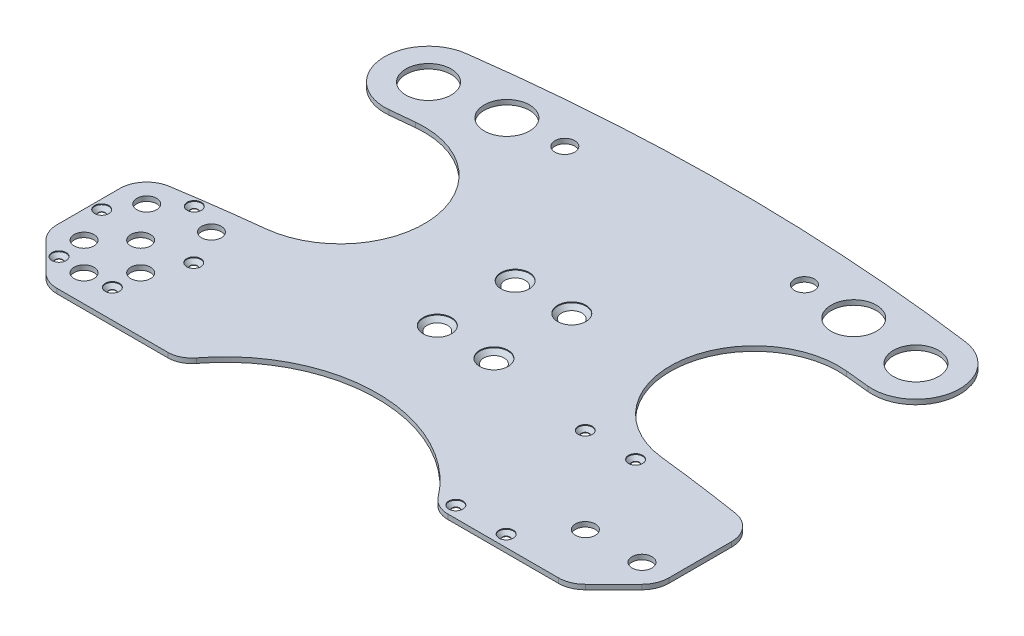
SolidWorks part; units mm, degrees
ref_plane "Front Plane" through (0, 0, 0) normal (0, 0, 1) x (1, 0, 0)
ref_plane "Top Plane" through (0, 0, 0) normal (0, 1, 0) x (1, 0, 0)
ref_plane "Right Plane" through (0, 0, 0) normal (1, 0, 0) x (0, 0, -1)
sketch "Sketch1" plane through (0, 0, 0) normal (0, 1, 0) x (1, 0, 0)
  line L1 (-120, -95) -> (120, -95)
  line L2 (-120, -95) -> (-120, 95)
  line L3 (-120, 95) -> (120, 95)
  line L4 (120, -95) -> (120, 95)
  line L5 (-120, -95) -> (120, 95) construction
  line L6 (-120, 95) -> (120, -95) construction
  line L7 (-10, 13.75) -> (10, 13.75)
  line L8 (-10, 13.75) -> (-10, -13.75)
  line L9 (-10, -13.75) -> (10, -13.75)
  line L10 (10, 13.75) -> (10, -13.75)
  line L11 (-10, 13.75) -> (10, -13.75) construction
  line L12 (-10, -13.75) -> (10, 13.75) construction
  circle A0 centre (0, 0) radius 95
  circle A1 centre (-10, 13.75) radius 2.5
  circle A2 centre (10, 13.75) radius 2.5
  circle A3 centre (10, -13.75) radius 2.5
  circle A4 centre (-10, -13.75) radius 2.5
  circle A5 centre (0, 0) radius 120
  dimension "D3" = 5
  dimension "D1" = 240
  dimension "D2" = 190
  dimension "D4" = 27.5
  dimension "D5" = 20
extrude "Boss-Extrude1" add sketch "Sketch1" along normal blind 1.7 contours A0 A4 L8 A1 L7 A2 L10 A3 L9 | A4 L9 A3 L10 A2 L7 A1 L8 | L3 A5 L1 A0 | L1 A5 L3 A0 region at (-105.6812, 0, 51.9346) region at (68.7642, 0, 68.7642) region at (-92.313, 0, 0) region at (0, 0, 0)
sketch "Sketch2" plane through (0, 1.7, 0) normal (0, 1, 0) x (1, 0, 0)
  line L0 (-81.1673, -40) -> (21.9115, -40) construction
  line L1 (-127.3056, -60) -> (138.909, -60) construction
  line L2 (-88.5406, 28.139) -> (-88.5406, -89.0376) construction
  line L3 (-88.5406, -40) -> (-88.5406, -60) construction
  line L4 (0, 21.6044) -> (0, -21.4213) construction
  line L5 (88.5406, 33.139) -> (88.5406, -84.0376) construction
  line L6 (-151.9803, -25) -> (55.006, -25) construction
  line L7 (-48.8837, 35) -> (62.426, 35) construction
  circle A0 centre (0, 0) radius 35
  circle A1 centre (0, 35) radius 2.5
  circle A2 centre (30.3109, 17.5) radius 2.5
  circle A3 centre (30.3109, -17.5) radius 2.5
  circle A4 centre (0, -35) radius 2.5
  circle A5 centre (-30.3109, -17.5) radius 2.5
  circle A6 centre (-30.3109, 17.5) radius 2.5
  circle A7 centre (-88.5406, -40) radius 3.5
  circle A8 centre (-88.5406, -50) radius 10
  circle A9 centre (-78.5406, -50) radius 3.5
  circle A10 centre (-88.5406, -60) radius 3.5
  circle A11 centre (-98.5406, -50) radius 3.5
  circle A12 centre (78.5406, -50) radius 3.5
  circle A13 centre (98.5406, -50) radius 3.5
  circle A14 centre (-98.5406, -27.8625) radius 3.5
  circle A15 centre (-78.5406, -25) radius 3.5
  circle A16 centre (0, 0) radius 45
  circle A17 centre (0, -580) radius 625
  circle A18 centre (0, -580) radius 645
  circle A19 centre (-86.0945, 59.2282) radius 8
  circle A20 centre (-61.2596, 62.0843) radius 8
  circle A21 centre (-86.0945, 59.2282) radius 15.5
  arc A22 (-73.3144, 95) -> (-73.3144, -95) centre (0, 0) ccw construction
  circle A23 centre (-61.2596, 62.0843) radius 9.5
  circle A24 centre (-86.0945, 59.2282) radius 9.5
  circle A25 centre (61.2596, 62.0843) radius 8
  circle A26 centre (86.0945, 59.2282) radius 8
  circle A27 centre (-42.3209, 63.6101) radius 3.5
  circle A28 centre (0, 0) radius 70
  circle A29 centre (42.3209, 63.6101) radius 3.5
  circle A30 centre (-98.5406, -50) radius 9.5
  circle A31 centre (42.3209, 63.6101) radius 9.5
  circle A32 centre (61.2596, 62.0843) radius 9.5
  circle A33 centre (0, -645.0455) radius 625
  point P17 (0, 0)
  point P21 (-88.5406, -50)
  point P37 (-88.5406, -50)
  point P56 (0, 65)
  point P57 (0, 45)
  point P68 (-76.6704, 60.4269)
  point P69 (-70.7097, 61.1124)
  point P81 (0, 0)
  point P85 (-98.5406, -27.8625)
  dimension "D1" = 70
  dimension "D2" = 5
  dimension "D4" = 7
  dimension "D9" = 90
  dimension "D10" = 1250
  dimension "D11" = 20
  dimension "D12" = 16
  dimension "D14" = 6
  dimension "D13" = 19
  dimension "D17" = 140
  dimension "D18" = 6
  dimension "D5" = 20
  dimension "D6" = 40
  dimension "D8" = 15
  dimension "D15" = 6
  dimension "D3" = 6
  dimension "D7" = 4
extrude "Cut-Extrude1" cut sketch "Sketch2" against normal up to next contours A7 | A9 | A10 | A11 | A12 | A13 | A14 | A15 | A19 | A20 | A25 | A26 | A27 | A29
sketch "Sketch3" plane through (0, 1.7, 0) normal (0, 1, 0) x (1, 0, 0)
  line L1 (-84.5506, 43.8053) -> (-40.7771, 48.1872)
  line L2 (0, 100.6986) -> (0, -98.8678) construction
  line L3 (-10.3445, 0) -> (20.4144, 0) construction
  line L5 (84.5506, 43.8053) -> (40.7771, 48.1872)
  line L6 (-42.3209, 63.6101) -> (0, 0) construction
  line L7 (-36.306, 26.5871) -> (-55.2257, 55.0243)
  line L8 (-10.4964, 43.7587) -> (-29.4161, 72.1959)
  line L9 (10.4964, 43.7587) -> (29.4161, 72.1959)
  line L10 (36.306, 26.5871) -> (55.2257, 55.0243)
  line L11 (-108.0406, -50) -> (-108.0406, -27.8625)
  line L13 (-73.3144, -95) -> (73.3144, -95)
  line L14 (73.3144, 95) -> (-73.3144, 95)
  line L15 (-73.3144, -95) -> (73.3144, -95)
  line L16 (73.3144, 95) -> (-73.3144, 95)
  line L17 (-69.0406, -25) -> (-69.0406, -50)
  line L18 (-71.8231, -56.7175) -> (-81.8231, -66.7175)
  line L19 (-105.2581, -56.7175) -> (-95.2581, -66.7175)
  line L20 (-42.3209, 79.1101) -> (42.3209, 79.1101)
  line L21 (-78.5406, -15.5) -> (-42.2463, -15.5)
  line L22 (0, -45) -> (111.243, -45) construction
  line L23 (-88.5406, -69.5) -> (88.5406, -69.5)
  line L24 (69.0406, -15.5) -> (45.0406, -15.5)
  line L25 (78.5406, -15.5) -> (42.2463, -15.5)
  line L27 (108.0406, -50) -> (108.0406, -27.8625)
  line L28 (105.2581, -56.7175) -> (95.2581, -66.7175)
  line L29 (69.0406, -15.5) -> (69.0406, -69.5)
  line L30 (69.0406, -69.5) -> (45.0406, -69.5)
  line L31 (45.0406, -15.5) -> (45.0406, -69.5)
  line L32 (57.0406, -15.5) -> (57.0406, -69.5) construction
  line L33 (45.0406, -42.5) -> (69.0406, -42.5) construction
  circle A0 centre (-86.0945, 59.2282) radius 15.5
  arc A1 (-73.3144, 95) -> (-73.3144, -95) centre (0, 0) ccw construction
  circle A2 centre (-42.3209, 63.6101) radius 15.5
  circle A3 centre (86.0945, 59.2282) radius 15.5
  circle A4 centre (42.3209, 63.6101) radius 15.5
  circle A5 centre (0, 0) radius 45
  circle A6 centre (-98.5406, -27.8625) radius 9.5
  circle A7 centre (-98.5406, -27.8625) radius 3.5 construction
  arc A8 (-73.3144, 95) -> (-73.3144, -95) centre (0, 0) ccw
  arc A9 (73.3144, -95) -> (73.3144, 95) centre (0, 0) ccw
  arc A10 (-73.3144, 95) -> (-73.3144, -95) centre (0, 0) ccw
  arc A11 (73.3144, -95) -> (73.3144, 95) centre (0, 0) ccw
  circle A12 centre (-78.5406, -25) radius 9.5
  circle A13 centre (-88.5406, -60) radius 9.5
  circle A14 centre (-98.5406, -50) radius 9.5
  circle A15 centre (-78.5406, -50) radius 9.5
  circle A17 centre (98.5406, -50) radius 9.5
  circle A18 centre (78.5406, -50) radius 9.5
  arc A19 (73.3144, -95) -> (73.3144, 95) centre (0, 0) ccw construction
  arc A20 (-45.0406, -69.5) -> (45.0406, -69.5) centre (0, -98.6511) cw
  circle A21 centre (98.5406, -27.8625) radius 9.5
  circle A22 centre (98.5406, -50) radius 9.5
  circle A23 centre (88.5406, -60) radius 9.5
  circle A24 centre (-73.1485, 15.1063) radius 29.692
  circle A25 centre (73.1485, 15.1063) radius 29.692
  circle A26 centre (48.1506, -19.64) radius 1.3
  circle A27 centre (65.9306, -19.64) radius 1.3
  circle A28 centre (65.9306, -65.36) radius 1.3
  circle A29 centre (48.1506, -65.36) radius 1.3
  circle A30 centre (0, -580) radius 645
  circle A31 centre (0, -580) radius 660.5
  circle A32 centre (0, -645.0455) radius 634.5
  point P20 (0, -659.5242)
  arc M45 (-73.3144, 95) -> (-73.3144, -95) centre (0, 0) ccw
  line M46 (-73.3144, -95) -> (73.3144, -95)
  arc M47 (73.3144, -95) -> (73.3144, 95) centre (0, 0) ccw
  line M48 (73.3144, 95) -> (-73.3144, 95)
  dimension "D1" = 90
  dimension "D3" = 6
  dimension "D5" = 2.6
  dimension "D4" = 24
  dimension "D6" = 17.78
  dimension "D7" = 45.72
  dimension "D2" = 0
extrude "Cut-Extrude2" cut sketch "Sketch3" against normal up to next contours A24 L1 A0 A14 L11 A6 L21 M45 | A24 | L28 A23 L23 A13 L19 A14 A10 A17 M46 M47 | A20 L23 | L5 A25 L24 L25 A21 L27 A17 A11 A3 | A25 | A30 A0 M45 | A31 A11 M48 M45 | A0 A31 A10 | A31 A3 M47 | A30 A3 M47 | A6 A32 A14 L11 M45 | A11 A32 A21 L27 A17 | A26 | A27 | A28 | A29 region at (-105.8887, 1.7, -12.959) region at (-73.1485, 1.7, -15.1063) region at (-102.839, 1.7, -59.5932) region at (-94.2652, 1.7, -72.7135) region at (0, 1.7, -86.2332) region at (-111.2756, 1.7, 31.2797) region at (0, 1.7, 81.3426) region at (0, 1.7, 59.4787) region at (73.1485, 1.7, -15.1063) region at (105.8887, 1.7, -12.959) region at (111.2756, 1.7, 31.2797) region at (94.2652, 1.7, -72.7135) region at (102.839, 1.7, -59.5932)
fillet "Fillet1" radius 8.5 2 edges at (45.0406, 0.85, 69.5) (-45.0406, 0.85, 69.5)
sketch "Sketch8" plane through (0, 1.7, 0) normal (0, 1, 0) x (1, 0, 0)
  circle A8 centre (-89.4377, -20.1635) radius 1.25
  circle A9 centre (-104.7906, -37.5) radius 1.25
  circle A10 centre (-72.2906, -37.5) radius 1.25
  circle A11 centre (-97.96, -59.4194) radius 1.25
  circle A13 centre (-89.4377, -20.1635) radius 1.75 construction
  circle A14 centre (-72.2906, -37.5) radius 1.75 construction
  circle A15 centre (-104.7906, -37.5) radius 1.75 construction
  circle A16 centre (-97.96, -59.4194) radius 1.75 construction
  circle A17 centre (-79.1212, -59.4194) radius 1.25
  circle A18 centre (-79.1212, -59.4194) radius 1.75 construction
  dimension "D1" = 2.5
extrude "Cut-Extrude3" cut sketch "Sketch8" against normal up to next contours A8 | A10 | A9 | A11 | A17
hole_wizard "CSK for M5 Flat Head Machine Screw1" positions "Sketch4" profile "Sketch5" countersink size "M5" standard "ANSI Metric"
sketch "Sketch4" plane through (0, 1.7, 0) normal (0, 1, 0) x (1, 0, 0)
  point P0 (-10, 13.75)
  point P3 (10, 13.75)
  point P6 (10, -13.75)
  point P9 (-10, -13.75)
sketch "Sketch5" plane through (-10, 1.7, -13.75) normal (1, 0, 0) x (0, 0, 1)
  line L0 (0, 0) -> (0, 6.5022)
  line L1 (0, 6.5022) -> (2.5, 5)
  line L2 (2.5, 5) -> (2.5, 2.8)
  line L3 (2.5, 2.8) -> (5, 0.3)
  line L4 (5, 0.3) -> (5, 0)
  line L6 (5, 0) -> (0, 0)
  line L7 (-2.5, 2.8) -> (-5, 0.3) construction
  line L10 (0, 6.5022) -> (-2.5, 5) construction
  line L11 (0, -6.35) -> (0, 107.95) construction
  dimension "Hole Dia." = 5
  dimension "Hole Depth" = 5
  dimension "C'Sink Dia." = 10
  dimension "C'Sink Angle" = 90
  dimension "Drill Angle" = 118
  dimension "Head Clearance" = 0.3
hole_wizard "CSK for M2.5 Flat Head Machine Screw1" positions "Sketch6" profile "Sketch7" countersink size "M2.5" standard "ANSI Metric"
sketch "Sketch6" plane through (0, 1.7, 0) normal (0, 1, 0) x (1, 0, 0)
  point P0 (48.1506, -19.64)
  point P3 (65.9306, -19.64)
  point P6 (65.9306, -65.36)
  point P9 (48.1506, -65.36)
  point P12 (-89.4377, -20.1635)
  point P15 (-72.2906, -37.5)
  point P18 (-104.7906, -37.5)
  point P21 (-97.96, -59.4194)
  point P24 (-79.1212, -59.4194)
sketch "Sketch7" plane through (48.1506, 1.7, 19.64) normal (1, 0, 0) x (0, 0, 1)
  line L0 (0, 0) -> (0, 5.7511)
  line L1 (0, 5.7511) -> (1.25, 5)
  line L2 (1.25, 5) -> (1.25, 1.55)
  line L3 (1.25, 1.55) -> (2.5, 0.3)
  line L4 (2.5, 0.3) -> (2.5, 0)
  line L6 (2.5, 0) -> (0, 0)
  line L7 (-1.25, 1.55) -> (-2.5, 0.3) construction
  line L10 (0, 5.7511) -> (-1.25, 5) construction
  line L11 (0, -6.35) -> (0, 107.95) construction
  dimension "Hole Dia." = 2.5
  dimension "Hole Depth" = 5
  dimension "C'Sink Dia." = 5
  dimension "C'Sink Angle" = 90
  dimension "Drill Angle" = 118
  dimension "Head Clearance" = 0.3
